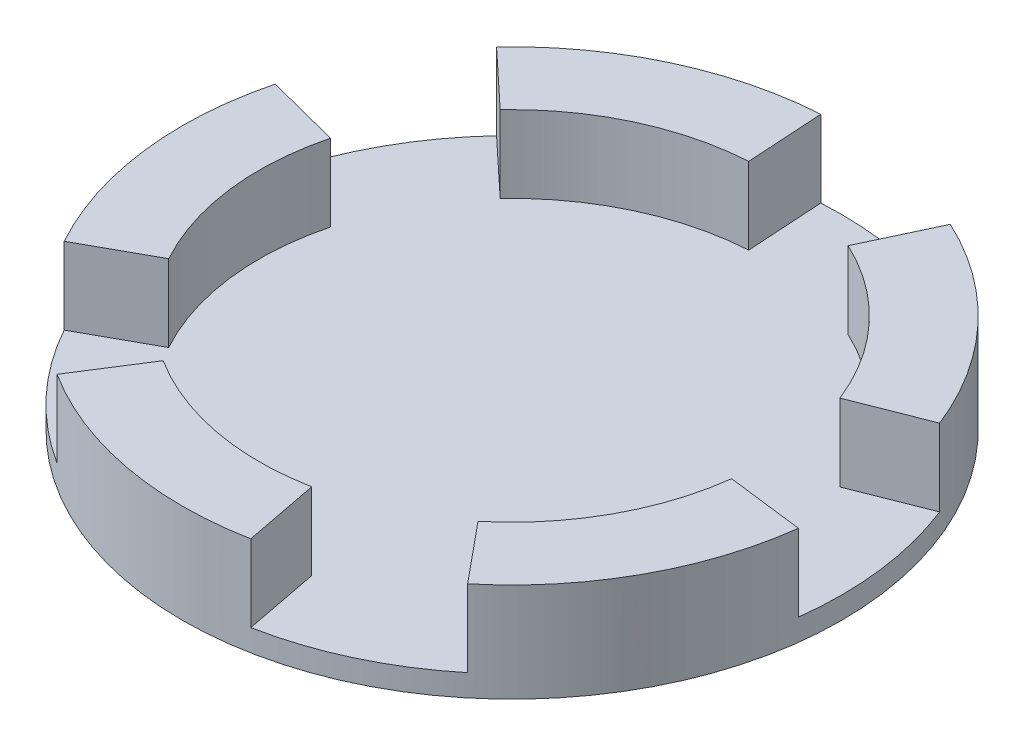
SolidWorks part; units mm, degrees
ref_plane "Front Plane" through (0, 0, 0) normal (0, 0, 1) x (1, 0, 0)
ref_plane "Top Plane" through (0, 0, 0) normal (0, 1, 0) x (1, 0, 0)
ref_plane "Right Plane" through (0, 0, 0) normal (1, 0, 0) x (0, 0, -1)
sketch "Sketch1" plane through (0, 0, 0) normal (0, 1, 0) x (1, 0, 0)
  line L0 (-1.7706, 2.575) -> (1.7706, 2.575)
  line L2 (0, 0) -> (1.9794, 0) construction
  line L3 (0.8555, 2.575) -> (0.8555, 0) construction
  line L4 (0.8555, 0) -> (0.8555, -2.575) construction
  line L5 (0, 2.575) -> (0, -3.9195) construction
  circle A0 centre (0, 0) radius 3.125 construction
  arc A1 (-1.7706, 2.575) -> (1.7706, 2.575) centre (0, 0) ccw
  circle A3 centre (0, 0) radius 5
  point P4 (0, -3.125)
  point P12 (0, 0)
  point P14 (0, 0)
  dimension "D1" = 6.25
  dimension "D3" = 10
  dimension "D2" = 5.7
extrude "Boss-Extrude1" add sketch "Sketch1" along normal blind 7.75
sketch "Sketch2" plane through (0, 7.75, 0) normal (0, 1, 0) x (1, 0, 0)
  circle A1 centre (0, 0) radius 5
  circle A2 centre (0, 0) radius 5
  dimension "D1" = 0
extrude "Boss-Extrude2" add sketch "Sketch2" along normal blind 5
sketch "Sketch3" plane through (0, 12.75, 0) normal (0, 1, 0) x (1, 0, 0)
  circle A0 centre (0, 0) radius 30
  dimension "D2" = 60
extrude "Boss-Extrude3" add sketch "Sketch3" along normal blind 2
fillet "Fillet1" radius 6 1 edges at (0, 12.75, 5)
sketch "Sketch4" plane through (0, 14.75, 0) normal (0, 1, 0) x (1, 0, 0)
  line L0 (0, 0) -> (-16.7954, 15.7135) construction
  line L1 (0, 0) -> (9.7544, 20.8291) construction
  line L2 (0, 0) -> (21.3954, 8.4401) construction
  line L3 (0, 0) -> (22.8239, -2.8404) construction
  line L4 (0, 0) -> (14.6386, -17.7401) construction
  line L5 (0, 0) -> (4.3516, -22.5846) construction
  line L6 (0, 0) -> (-12.3483, -19.4041) construction
  line L7 (0, 0) -> (-20.1345, -11.1176) construction
  line L8 (0, 0) -> (-22.2702, 5.7477) construction
  line L9 (0, 0) -> (-1.4155, 22.9564) construction
  line L10 (-16.7954, 15.7135) -> (-1.4155, 22.9564) construction
  line L11 (-1.4155, 22.9564) -> (9.7544, 20.8291) construction
  line L12 (9.7544, 20.8291) -> (21.3954, 8.4401) construction
  line L13 (21.3954, 8.4401) -> (22.8239, -2.8404) construction
  line L14 (22.8239, -2.8404) -> (14.6386, -17.7401) construction
  line L15 (14.6386, -17.7401) -> (4.3516, -22.5846) construction
  line L16 (4.3516, -22.5846) -> (-12.3483, -19.4041) construction
  line L17 (-12.3483, -19.4041) -> (-20.1345, -11.1176) construction
  line L18 (-20.1345, -11.1176) -> (-22.2702, 5.7477) construction
  line L19 (-22.2702, 5.7477) -> (-16.7954, 15.7135) construction
  line L20 (14.6386, -17.7401) -> (19.0938, -23.1393)
  line L21 (22.8239, -2.8404) -> (29.7703, -3.7049)
  line L22 (21.3954, 8.4401) -> (27.9071, 11.0089)
  line L23 (9.7544, 20.8291) -> (12.7231, 27.1684)
  line L24 (-1.4155, 22.9564) -> (-1.8463, 29.9431)
  line L25 (-16.7954, 15.7135) -> (-21.907, 20.4959)
  line L26 (-22.2702, 5.7477) -> (-29.0482, 7.497)
  line L27 (-20.1345, -11.1176) -> (-26.2624, -14.5012)
  line L28 (-12.3483, -19.4041) -> (-16.1064, -25.3097)
  line L29 (4.3516, -22.5846) -> (5.676, -29.4582)
  circle A0 centre (0, 0) radius 23 construction
  arc A1 (-16.7954, 15.7135) -> (-1.4155, 22.9564) centre (0, 0) cw
  arc A2 (9.7544, 20.8291) -> (21.3954, 8.4401) centre (0, 0) cw
  arc A3 (22.8239, -2.8404) -> (14.6386, -17.7401) centre (0, 0) cw
  arc A4 (-12.3483, -19.4041) -> (4.3516, -22.5846) centre (0, 0) ccw
  arc A5 (-20.1345, -11.1176) -> (-22.2702, 5.7477) centre (0, 0) cw
  arc A6 (-1.8463, 29.9431) -> (-21.907, 20.4959) centre (0, 0) ccw
  arc A7 (-29.0482, 7.497) -> (-26.2624, -14.5012) centre (0, 0) ccw
  arc A8 (5.676, -29.4582) -> (-16.1064, -25.3097) centre (0, 0) cw
  arc A9 (12.7231, 27.1684) -> (27.9071, 11.0089) centre (0, 0) cw
  arc A10 (29.7703, -3.7049) -> (19.0938, -23.1393) centre (0, 0) cw
  circle A11 centre (0, 0) radius 30 construction
  dimension "D1" = 46
  dimension "D2" = 17
extrude "Boss-Extrude4" add sketch "Sketch4" along normal blind 7
sketch "Sketch5" plane through (0, 0, 0) normal (0, -1, 0) x (1, 0, 0)
  line L0 (3.6853, 3.3791) -> (6.7836, 0)
  line L1 (6.7836, 0) -> (4.236, -2.6564)
  line L2 (4.236, -2.6564) -> (0.0726, -6.9975)
  line L3 (0.0726, -6.9975) -> (-7.1672, -0.054)
  line L4 (-7.1672, -0.054) -> (0.1771, 7.2053)
  line L5 (0.1771, 7.2053) -> (3.6853, 3.3791)
  circle A1 centre (0, 0) radius 5
  circle A2 centre (0, 0) radius 5
  circle M8 centre (0, 0) radius 5
  dimension "D1" = 0
extrude "Boss-Extrude5" add sketch "Sketch5" against normal up to surface (6.75 mm away) contours L4 L3 M8 | L5 L4 M8 | L1 L0 M8 | L3 L2 M8 region at (0.1358, 0, 5.5262) region at (5.4354, 0, 0.0817) region at (-5.517, 0, -0.0416) region at (-0.0223, 0, -5.4923) up to face at (0, 6.75, 5)
